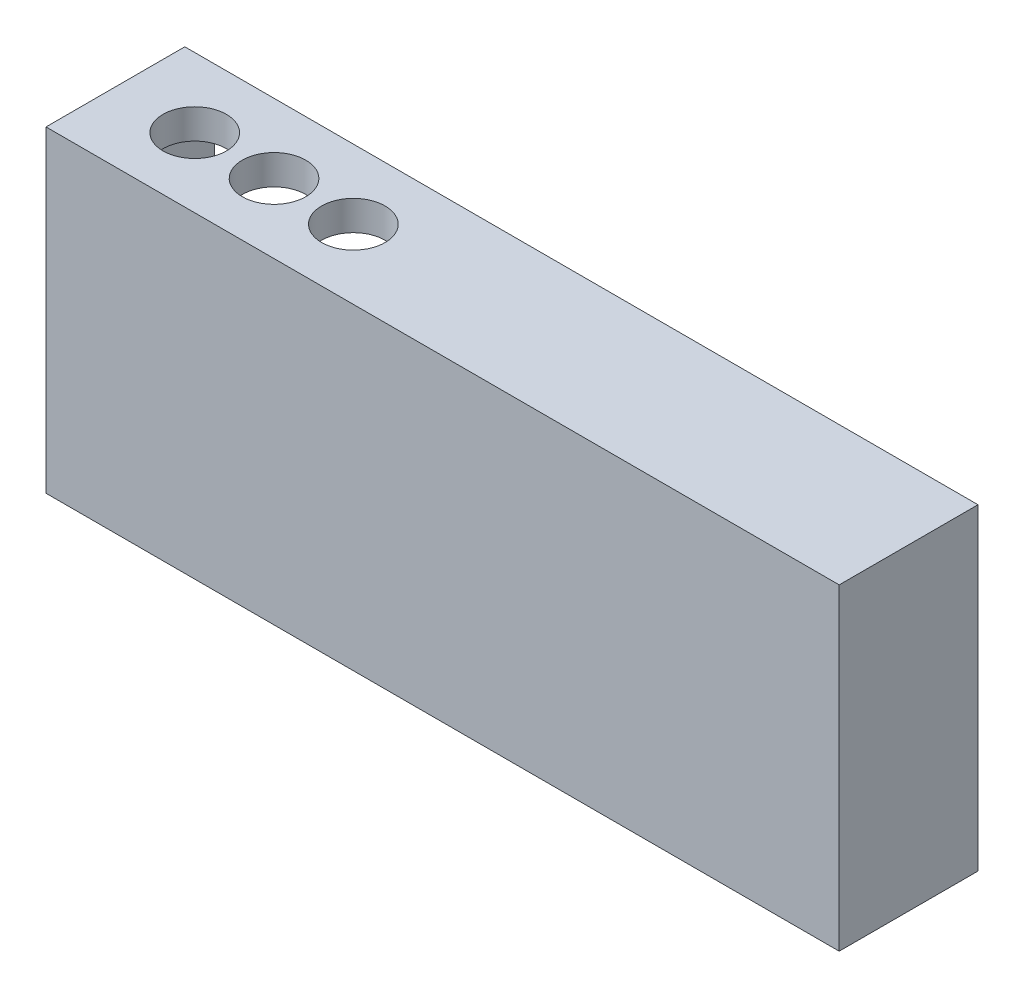
SolidWorks part; units mm, degrees
ref_plane "Alzado" through (0, 0, 0) normal (0, 0, 1) x (1, 0, 0)
ref_plane "Planta" through (0, 0, 0) normal (0, 1, 0) x (1, 0, 0)
ref_plane "Vista lateral" through (0, 0, 0) normal (1, 0, 0) x (0, 0, -1)
sketch "Croquis1" plane through (0, 0, 0) normal (0, 0, 1) x (1, 0, 0)
  line L1 (-100, -40) -> (100, -40)
  line L2 (-100, -40) -> (-100, 40)
  line L3 (-100, 40) -> (100, 40)
  line L4 (100, -40) -> (100, 40)
  line L5 (-100, -40) -> (100, 40) construction
  line L6 (-100, 40) -> (100, -40) construction
  point P0 (0, 0)
  dimension "D1" = 200
  dimension "D2" = 80
extrude "Saliente-Extruir1" add sketch "Croquis1" along normal blind 35
sketch "Croquis2" plane through (0, 0, 0) normal (0, 0, -1) x (-1, 0, 0)
  line L1 (-92.5, -32.5) -> (92.5, -32.5)
  line L2 (-92.5, -32.5) -> (-92.5, 32.5)
  line L3 (-92.5, 32.5) -> (92.5, 32.5)
  line L4 (92.5, -32.5) -> (92.5, 32.5)
  line L5 (-92.5, -32.5) -> (92.5, 32.5) construction
  line L6 (-92.5, 32.5) -> (92.5, -32.5) construction
  point P1 (0, 0)
  dimension "D1" = 185
  dimension "D2" = 65
extrude "Cortar-Extruir1" cut sketch "Croquis2" against normal blind 27.5
sketch "Croquis3" plane through (0, 40, 0) normal (0, 1, 0) x (1, 0, 0)
  line L0 (-100, -17.5) -> (100, -17.5) construction
  line L1 (-100, -35) -> (-100, 0) construction
  line L2 (100, -35) -> (100, 0) construction
  circle A0 centre (-80, -17.5) radius 8
  circle A1 centre (-60, -17.5) radius 8
  circle A2 centre (-40, -17.5) radius 8
  dimension "D1" = 16
  dimension "D2" = 16
  dimension "D3" = 16
  dimension "D4" = 20
  dimension "D5" = 20
  dimension "D6" = 20
extrude "Cortar-Extruir2" cut sketch "Croquis3" against normal blind 7.5
sketch "Croquis4" plane through (0, -40, 0) normal (0, -1, 0) x (1, 0, 0)
  line L0 (100, 17.5) -> (-100, 17.5) construction
  line L1 (100, 35) -> (100, 0) construction
  line L2 (-100, 35) -> (-100, 0) construction
  circle A0 centre (80, 17.5) radius 5.4
  dimension "D1" = 10.8
  dimension "D2" = 20
extrude "Cortar-Extruir3" cut sketch "Croquis4" against normal blind 7.5
sketch "Croquis5" plane through (0, 0, 0) normal (0, 0, -1) x (-1, 0, 0)
  line L0 (100, 40) -> (100, -40) construction
  line L1 (100, -40) -> (-100, -40) construction
  circle A0 centre (96.25, -36.25) radius 2.5092
  circle A1 centre (-96.25, -36.25) radius 2.5092
  circle A2 centre (-96.25, 36.25) radius 2.5092
  circle A3 centre (96.25, 36.25) radius 2.5092
  dimension "D1" = 5.0184
  dimension "D2" = 3.75
  dimension "D3" = 3.75
  dimension "D4" = 2
  dimension "D5" = 2
extrude "Cortar-Extruir4" cut sketch "Croquis5" against normal blind 2 contours A0 | A3 | A2 | A1 region at (-96.25, -36.25, 0) region at (96.25, -36.25, 0) region at (96.25, 36.25, 0) region at (-96.25, 36.25, 0)
